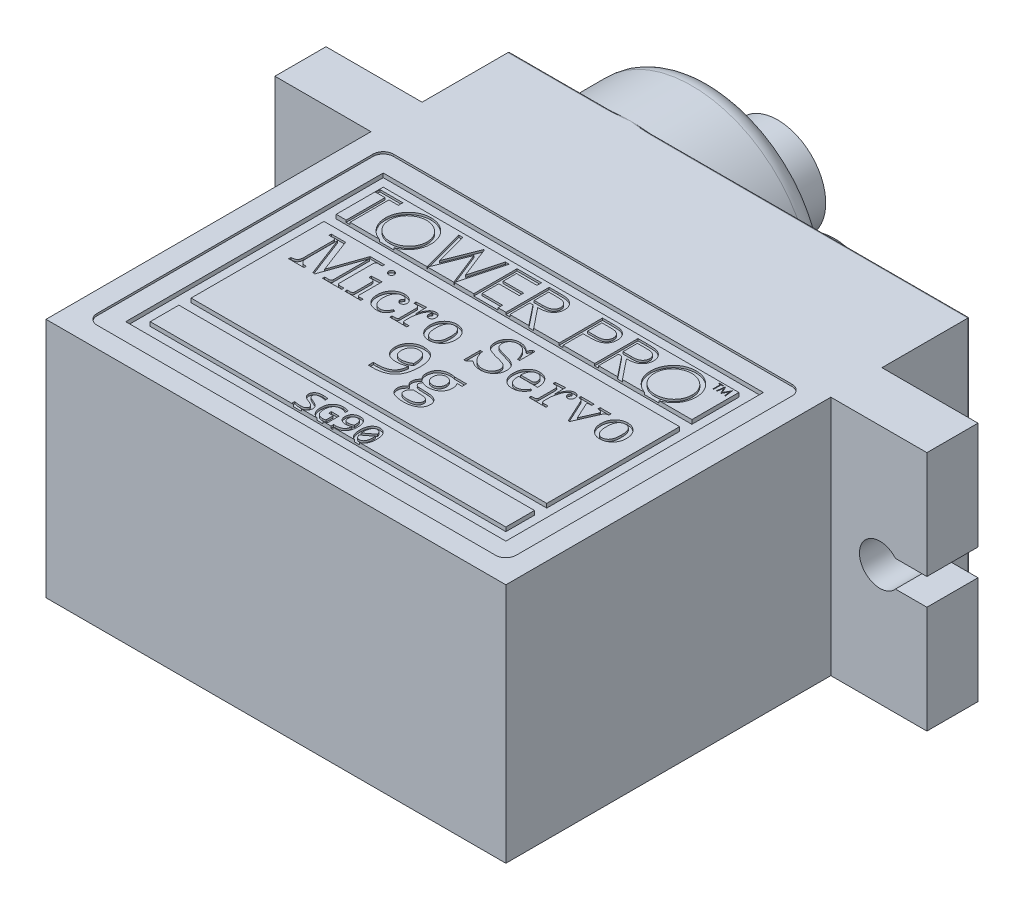
SolidWorks part; units mm, degrees
ref_plane "Front Plane" through (0, 0, 0) normal (0, 0, 1) x (1, 0, 0)
ref_plane "Top Plane" through (0, 0, 0) normal (0, 1, 0) x (1, 0, 0)
ref_plane "Right Plane" through (0, 0, 0) normal (1, 0, 0) x (0, 0, -1)
sketch "Sketch1" plane through (0, 0, 0) normal (0, 1, 0) x (1, 0, 0)
  line L1 (-11.25, -11.35) -> (11.25, -11.35)
  line L2 (-11.25, -11.35) -> (-11.25, 11.35)
  line L3 (-11.25, 11.35) -> (11.25, 11.35)
  line L4 (11.25, -11.35) -> (11.25, 11.35)
  line L5 (-11.25, -11.35) -> (11.25, 11.35) construction
  line L6 (-11.25, 11.35) -> (11.25, -11.35) construction
  point P0 (0, 0)
  dimension "D1" = 22.5
  dimension "D2" = 22.7
extrude "Boss-Extrude1" add sketch "Sketch1" along normal mid plane 11.8
sketch "Sketch2" plane through (11.25, 0, 0) normal (1, 0, 0) x (0, 0, -1)
  line L0 (-11.35, -5.9) -> (11.35, -5.9) construction
  line L1 (7.05, -5.9) -> (4.55, -5.9)
  line L2 (7.05, -5.9) -> (7.05, 5.9)
  line L3 (7.05, 5.9) -> (4.55, 5.9)
  line L4 (4.55, -5.9) -> (4.55, 5.9)
  line L5 (-11.35, 5.9) -> (11.35, 5.9) construction
  line L6 (-11.35, 5.9) -> (-11.35, -5.9) construction
  dimension "D1" = 2.5
  dimension "D2" = 15.9
extrude "Boss-Extrude2" add sketch "Sketch2" along normal blind 4.7
sketch "Sketch3" plane through (-11.25, 0, 0) normal (-1, 0, 0) x (0, 0, 1)
  line L0 (-11.35, -5.9) -> (11.35, -5.9) construction
  line L1 (-7.05, -5.9) -> (-4.55, -5.9)
  line L2 (-7.05, -5.9) -> (-7.05, 5.9)
  line L3 (-7.05, 5.9) -> (-4.55, 5.9)
  line L4 (-4.55, -5.9) -> (-4.55, 5.9)
  line L5 (-11.35, 5.9) -> (11.35, 5.9) construction
  line L6 (11.35, 5.9) -> (11.35, -5.9) construction
  dimension "D1" = 15.9
  dimension "D2" = 2.5
extrude "Boss-Extrude3" add sketch "Sketch3" along normal blind 4.7
sketch "Sketch4" plane through (0, 0, -11.35) normal (0, 0, -1) x (-1, 0, 0)
  line L0 (11.25, 5.9) -> (11.25, -5.9) construction
  line L1 (-11.25, -5.9) -> (11.25, -5.9) construction
  line L3 (-11.25, -5.9) -> (-11.25, 5.9) construction
  arc A0 (-0.0667, -2.3387) -> (-0.0667, 2.3387) centre (5.35, 0) ccw
  arc A1 (-0.0667, 2.3387) -> (-0.0667, -2.3387) centre (-0.95, 0) ccw
  point P11 (-3.45, 0)
  point P12 (-11.25, 0)
  dimension "D1" = 11.8
  dimension "D4" = 5
  dimension "D2" = 5.9
  dimension "D3" = 5.9
  dimension "D5" = 6.3
  dimension "D6" = 7.8
extrude "Boss-Extrude5" add sketch "Sketch4" along normal blind 4
sketch "Sketch7" plane through (0, 0, -7.05) normal (0, 0, -1) x (-1, 0, 0)
  line L0 (-15.95, -5.9) -> (-15.95, 5.9) construction
  line L1 (-14.4099, 0.65) -> (-15.95, 0.65)
  line L2 (-15.95, 0.65) -> (-15.95, -0.65)
  line L3 (-15.95, -0.65) -> (-14.4099, -0.65)
  line L4 (14.4099, 0.65) -> (15.95, 0.65)
  line L5 (15.95, 5.9) -> (15.95, -5.9) construction
  line L6 (15.95, 0.65) -> (15.95, -0.65)
  line L7 (15.95, -0.65) -> (14.4099, -0.65)
  line L10 (-15.95, 5.9) -> (-11.25, 5.9) construction
  line L11 (15.95, 5.9) -> (11.25, 5.9) construction
  line L12 (12.1344, 0) -> (15.1656, 0) construction
  line L13 (-12.15, 0) -> (-15.15, 0) construction
  arc A0 (-14.4099, -0.65) -> (-14.4099, 0.65) centre (-13.65, 0) ccw
  arc A1 (14.4099, 0.65) -> (14.4099, -0.65) centre (13.65, 0) ccw
  dimension "D3" = 2
  dimension "D4" = 2
  dimension "D1" = 5.9
  dimension "D2" = 5.9
  dimension "D5" = 2.3
  dimension "D6" = 2.3
  dimension "D7" = 0.65
  dimension "D8" = 0.65
  dimension "D9" = 3
  dimension "D10" = 0.65
  dimension "D11" = 0.65
extrude "Cut-Extrude6" cut sketch "Sketch7" against normal through all
sketch "Sketch11" plane through (0, 5.9, 0) normal (0, 1, 0) x (1, 0, 0)
  line L1 (-9.75, -10.35) -> (9.75, -10.35)
  line L2 (-10.25, -9.85) -> (-10.25, 3.65)
  line L3 (-9.75, 4.15) -> (9.75, 4.15)
  line L4 (10.25, -9.85) -> (10.25, 3.65)
  line L5 (-10.25, -10.35) -> (10.25, 4.15) construction
  line L6 (-10.25, 4.15) -> (10.25, -10.35) construction
  line L7 (-11.25, -11.35) -> (11.25, -11.35) construction
  line L8 (11.25, -11.35) -> (11.25, 4.55) construction
  line L9 (-11.25, 4.55) -> (-11.25, -11.35) construction
  arc A0 (-9.75, -10.35) -> (-10.25, -9.85) centre (-9.75, -9.85) cw
  arc A1 (9.75, -10.35) -> (10.25, -9.85) centre (9.75, -9.85) ccw
  arc A2 (9.75, 4.15) -> (10.25, 3.65) centre (9.75, 3.65) cw
  arc A3 (-10.25, 3.65) -> (-9.75, 4.15) centre (-9.75, 3.65) cw
  point P0 (0, -3.1)
  dimension "D1" = 0.5
  dimension "D2" = 13.5
  dimension "D3" = 1
  dimension "D4" = 1
  dimension "D5" = 1
extrude "Cut-Extrude7" cut sketch "Sketch11" against normal blind 0.1
fillet "Fillet8" radius 0.1 7 edges at (-11.25, 2.95, -11.35) (-11.25, -2.95, -11.35) (-8.3, -5.9, -11.35) (11.25, 0, -11.35) (2.95, -5.9, -11.35) (2.95, 5.9, -11.35) (-8.3, 5.9, -11.35)
sketch "Sketch18" plane through (0, 5.8, 0) normal (0, 1, 0) x (1, 0, 0)
  line L0 (-8.7, 0.3) -> (-8.7, 2.6)
  line L1 (8.7, -0.3) -> (8.7, -6.8)
  line L2 (8.7, -7.4) -> (8.7, -8.8)
  line L3 (-8.7, -6.8) -> (-8.7, -0.3)
  line L5 (9.75, 4.15) -> (-9.75, 4.15) construction
  line L6 (-10.25, 3.65) -> (-10.25, -9.85) construction
  line L7 (10.25, -9.85) -> (10.25, 3.65) construction
  line L10 (-9.3, 3.2) -> (9.3, 3.2)
  line L11 (9.3, 3.2) -> (9.3, -9.4)
  line L12 (9.3, -9.4) -> (-9.3, -9.4)
  line L13 (-9.3, -9.4) -> (-9.3, 3.2)
  line L14 (-8.7, -0.3) -> (8.7, -0.3)
  line L15 (-8.7, -7.4) -> (8.7, -7.4)
  line L16 (-8.7, 2.6) -> (8.7, 2.6)
  line L17 (8.7, 2.6) -> (8.7, 0.3)
  line L18 (8.7, -8.8) -> (-8.7, -8.8)
  line L19 (-8.7, -8.8) -> (-8.7, -7.4)
  line L20 (-8.7, 0.3) -> (8.7, 0.3)
  line L21 (-8.7, -6.8) -> (8.7, -6.8)
  dimension "D1" = 12.6
  dimension "D2" = 17.4
  dimension "D3" = 17.4
  dimension "D4" = 17.4
  dimension "D5" = 18.6
  dimension "D6" = 17.4
  dimension "D7" = 17.4
  dimension "D8" = 17.4
  dimension "D9" = 1.4
  dimension "D10" = 0.95
  dimension "D11" = 0.6
  dimension "D12" = 0.6
  dimension "D13" = 0.95
  dimension "D14" = 0.95
  dimension "D15" = 0.6
  dimension "D16" = 0.6
extrude "Cut-Extrude16" cut sketch "Sketch18" against normal blind 0.2
sketch "Sketch19" plane through (0, 5.8, 0) normal (0, 1, 0) x (1, 0, 0)
  line L0 (7.7319, 2.119) -> (8.6448, 2.119) construction
  line L1 (8.7, 2.6) -> (-8.7, 2.6) construction
  line L3 (-8.7, -2.748) -> (8.6448, -2.748) construction
  line L4 (-8.7, -0.3) -> (-8.7, -6.8) construction
  line L5 (-8.7, -5.3084) -> (8.7, -5.3084) construction
  line L6 (8.7, -6.8) -> (8.7, -0.3) construction
  line L7 (8.7, -0.3) -> (-8.7, -0.3) construction
  line L8 (-8.7, -6.8) -> (8.7, -6.8) construction
  text T0 "TOWER PRO" font "Century Gothic" height in points 8
  text T1 "TM" font "Century Gothic" height 0.4
  text T2 "Micro Servo" font "Century" height in points 8
  text T3 "9g" font "Consolas" height in points 8
  text T4 "SG90" font "Consolas" height 1.096
  dimension "D1" = 0.9129
  dimension "D2" = 0.481
  dimension "D3" = 2.448
  dimension "D4" = 1.4916
extrude "Cut-Extrude17" cut sketch "Sketch19" against normal blind 0.1
fillet "Fillet9" radius 1 2 edges at (3.45, 0, -15.35) (-11.25, 0, -15.35)
sketch "Sketch20" plane through (0, 0, -15.35) normal (0, 0, -1) x (-1, 0, 0)
  circle A0 centre (5.35, 0) radius 2.35
  dimension "D1" = 4.7
extrude "Boss-Extrude6" add sketch "Sketch20" along normal blind 3.2
sketch "Sketch21" plane through (0, 0, -18.55) normal (0, 0, -1) x (-1, 0, 0)
  circle A0 centre (5.35, 0) radius 1
  dimension "D1" = 2
extrude "Cut-Extrude18" cut sketch "Sketch21" against normal blind 0.225
sketch "Sketch23" plane through (0, 0, -18.325) normal (0, 0, -1) x (-1, 0, 0)
  line L0 (5.35, -0.82) -> (5.35, 0.82) construction
  line L1 (5.17, -0.82) -> (5.17, -0.18)
  line L2 (5.53, -0.82) -> (5.53, -0.18)
  line L3 (6.17, 0) -> (4.53, 0) construction
  line L4 (6.17, -0.18) -> (5.53, -0.18)
  line L5 (6.17, 0.18) -> (5.53, 0.18)
  line L6 (5.17, 0.18) -> (4.53, 0.18)
  line L7 (5.53, 0.18) -> (5.53, 0.82)
  line L8 (5.17, -0.18) -> (4.53, -0.18)
  line L9 (5.17, 0.18) -> (5.17, 0.82)
  arc A0 (5.17, -0.82) -> (5.53, -0.82) centre (5.35, -0.82) ccw
  arc A1 (5.53, 0.82) -> (5.17, 0.82) centre (5.35, 0.82) ccw
  arc A2 (6.17, -0.18) -> (6.17, 0.18) centre (6.17, 0) ccw
  arc A3 (4.53, 0.18) -> (4.53, -0.18) centre (4.53, 0) ccw
  circle A4 centre (5.35, 0) radius 1 construction
  point P2 (5.35, 0)
  point P9 (5.35, 0)
  dimension "D1" = 0.18
  dimension "D2" = 0.18
  dimension "D3" = 0.18
  dimension "D4" = 0.18
  dimension "D5" = 0.64
  dimension "D6" = 0.64
  dimension "D7" = 0.64
  dimension "D8" = 0.64
  dimension "D9" = 0.64
  dimension "D10" = 0.64
  dimension "D11" = 0.64
  dimension "D12" = 0.36
extrude "Cut-Extrude19" cut sketch "Sketch23" against normal blind 1
